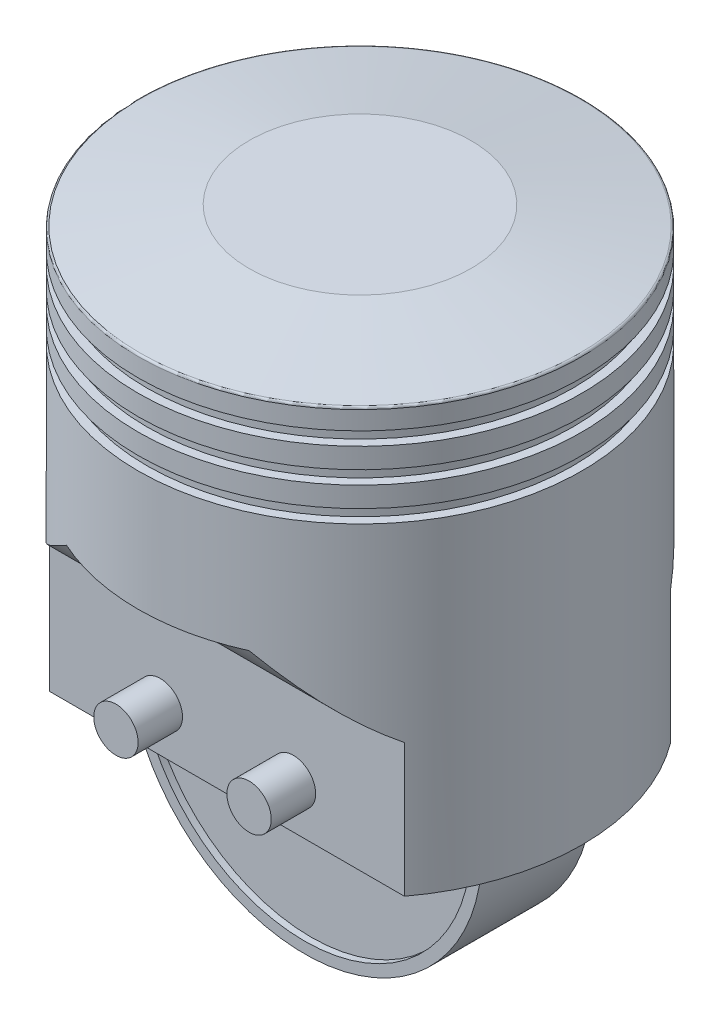
SolidWorks part; units mm, degrees
material "Malleable Cast Iron"
ref_plane "Front Plane" through (0, 0, 0) normal (0, 0, 1) x (1, 0, 0)
ref_plane "Top Plane" through (0, 0, 0) normal (0, 1, 0) x (1, 0, 0)
ref_plane "Right Plane" through (0, 0, 0) normal (1, 0, 0) x (0, 0, -1)
sketch "Sketch1" plane through (0, 0, 0) normal (0, 0, 1) x (1, 0, 0)
  line L0 (0, 0) -> (-50, 0)
  line L1 (27.5, 0) -> (-27.5, 0) construction
  line L2 (-50, 0) -> (-50, 73)
  line L3 (-50, 73) -> (-48, 73)
  line L4 (-48, 73) -> (-48, 76)
  line L5 (-50, 76) -> (-50, 80.58)
  line L6 (-50, 80.58) -> (-48, 80.58)
  line L7 (-48, 80.58) -> (-48, 83.58)
  line L8 (-48, 83.58) -> (-50, 83.58)
  line L9 (-50, 83.58) -> (-50, 88.16)
  line L10 (-50, 88.16) -> (-48, 88.16)
  line L11 (-48, 88.16) -> (-48, 91.16)
  line L12 (-48, 91.16) -> (-50, 91.16)
  line L13 (-50, 76) -> (-48, 76)
  line L14 (-50, 91.16) -> (-50, 95.3178)
  line L16 (0, 95.74) -> (0, 0)
  line L17 (0, 95.74) -> (0, 99.99)
  line L18 (0, -51.7389) -> (0, 51.7389) construction
  line L19 (0, 99.99) -> (-25, 99.99)
  line L20 (-25, 99.99) -> (-49.5838, 95.8108)
  arc A0 (-50, 95.3178) -> (-49.5838, 95.8108) centre (-49.5, 95.3178) cw
  point P28 (-50, 95.74)
  dimension "D19" = 0.5
  dimension "D1" = 50
  dimension "D2" = 73
  dimension "D3" = 2
  dimension "D4" = 3
  dimension "D5" = 2
  dimension "D6" = 4.58
  dimension "D7" = 3
  dimension "D8" = 4.58
  dimension "D9" = 3
  dimension "D10" = 4.58
  dimension "D11" = 4.25
  dimension "D12" = 25
  dimension "D13" = 25
  dimension "D14" = 22.74
  dimension "D15" = 4.25
  dimension "D16" = 10.58
  dimension "D17" = 48
  dimension "D18" = 50
revolve "Revolve2" add sketch "Sketch1" angle 360 about L16 region at (-24.7325, 49.3538, 0)
sketch "Sketch2" plane through (0, 0, 0) normal (1, 0, 0) x (0, 0, -1)
  line L0 (0, 0) -> (30, 0)
  line L1 (55, 0) -> (-55, 0) construction
  line L2 (30, 0) -> (30, 30)
  line L3 (50, 46) -> (50, 0)
  line L4 (45.57, 46) -> (50, 46)
  line L5 (50, 0) -> (50, 73) construction
  line L6 (50, 0) -> (30, 0)
  line L7 (0, 54.9945) -> (0, -54.9945) construction
  line L8 (-30, 0) -> (-30, 30)
  line L9 (-50, 0) -> (-30, 0)
  line L10 (-50, 46) -> (-50, 0)
  line L11 (-45.57, 46) -> (-50, 46)
  arc A0 (30, 30) -> (45.57, 46) centre (2.8559, 71.9904) ccw
  arc A1 (-30, 30) -> (-45.57, 46) centre (-2.8559, 71.9904) cw
  dimension "D5" = 50
  dimension "D1" = 4.43
  dimension "D2" = 30
  dimension "D3" = 46
  dimension "D4" = 30
extrude "Cut-Extrude2" cut sketch "Sketch2" against normal through all and the other way through all contours L11 L10 L9 L8 A1 | L2 A0 L4 L3 L6
sketch "Sketch4" plane through (0, 0, 0) normal (0, 0, 1) x (1, 0, 0)
  line L0 (-40, 0) -> (40, 0)
  line L1 (-37.4166, -2.5) -> (37.4166, -2.5)
  line L2 (0, -55) -> (0, 55) construction
  arc A0 (-40, 0) -> (40, 0) centre (0, 0) ccw
  circle A1 centre (-15, 10) radius 5
  arc A2 (-37.4166, -2.5) -> (37.4166, -2.5) centre (0, 0) ccw
  circle A3 centre (15, 10) radius 5
  dimension "D1" = 80
  dimension "D2" = 10
  dimension "D3" = 15
  dimension "D4" = 10
  dimension "D5" = 2.5
extrude "Boss-Extrude3" add sketch "Sketch4" along normal blind 12.5 and the other way blind 12.5 contours A2 L1 | A0 L0
extrude "Boss-Extrude4" add sketch "Sketch4<7>" along normal blind 11 and the other way blind 11 contours L1 A2
sketch "Sketch4<7>" plane through (0, 0, 0) normal (0, 0, 1) x (1, 0, 0) same geometry as "Sketch4"
extrude "Boss-Extrude5" add sketch "Sketch4<8>" along normal blind 40 and the other way blind 40 contours A1 | A3
sketch "Sketch4<8>" plane through (0, 0, 0) normal (0, 0, 1) x (1, 0, 0) same geometry as "Sketch4"
